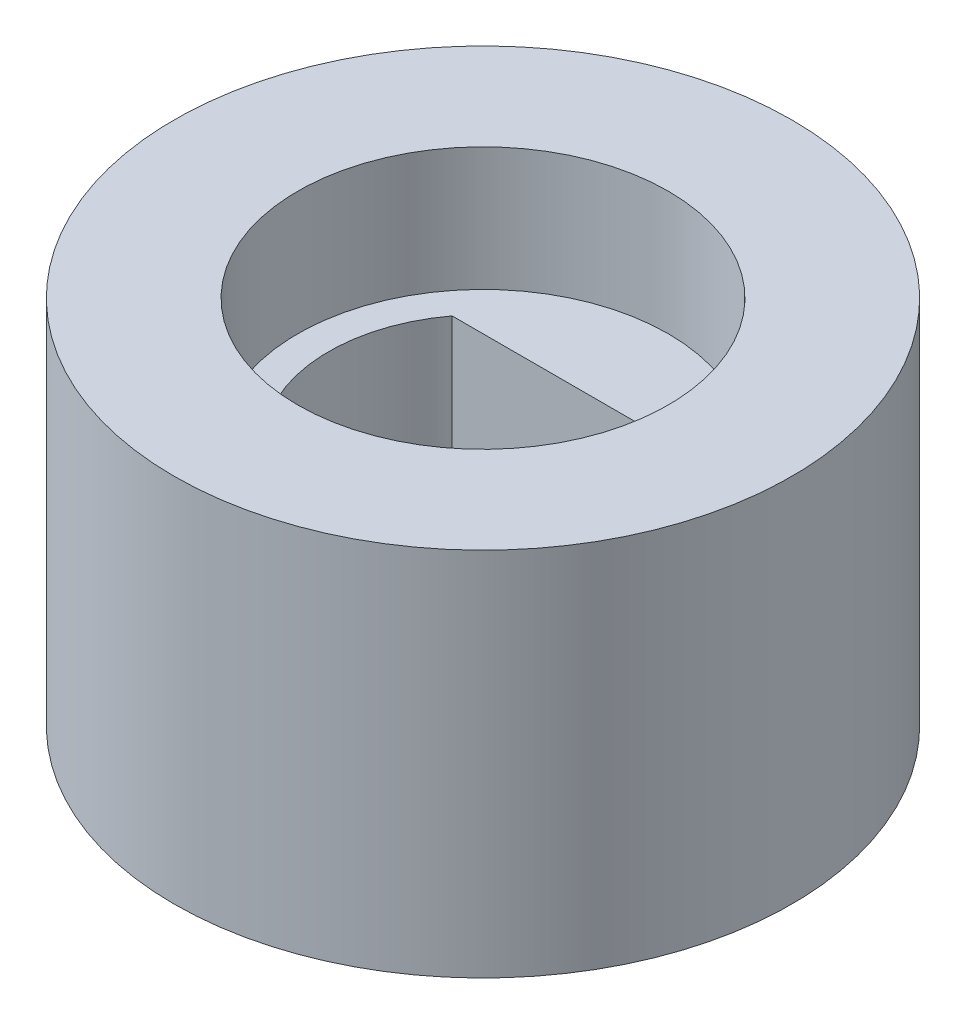
SolidWorks part; units mm, degrees
note: The reader was unsure of these and kept them because the rebuilt part matched: shared geometry of "草图1<3>".
ref_plane "前视基准面" through (0, 0, 0) normal (0, 0, 1) x (1, 0, 0)
ref_plane "上视基准面" through (0, 0, 0) normal (0, 1, 0) x (1, 0, 0)
ref_plane "右视基准面" through (0, 0, 0) normal (1, 0, 0) x (0, 0, -1)
sketch "草图1" plane through (0, 0, 0) normal (0, 1, 0) x (1, 0, 0)
  line L0 (-2, 1.5) -> (2, 1.5)
  arc A0 (-2, 1.5) -> (2, 1.5) centre (0, 0) ccw
  circle A1 centre (0, 0) radius 5
  circle A2 centre (0, 0) radius 3
  dimension "D1" = 5
  dimension "D2" = 6
  dimension "D3" = 10
  dimension "D4" = 1.5
extrude "凸台-拉伸1" add sketch "草图1" along normal blind 4 contours A1 A2 | A2 A0 L0
extrude "凸台-拉伸2" add sketch "草图1<3>" along normal blind 2 from surface contours A1 A2
sketch "草图1<3>" plane through (0, 0, 0) normal (0, 1, 0) x (1, 0, 0) same geometry as "草图1"
